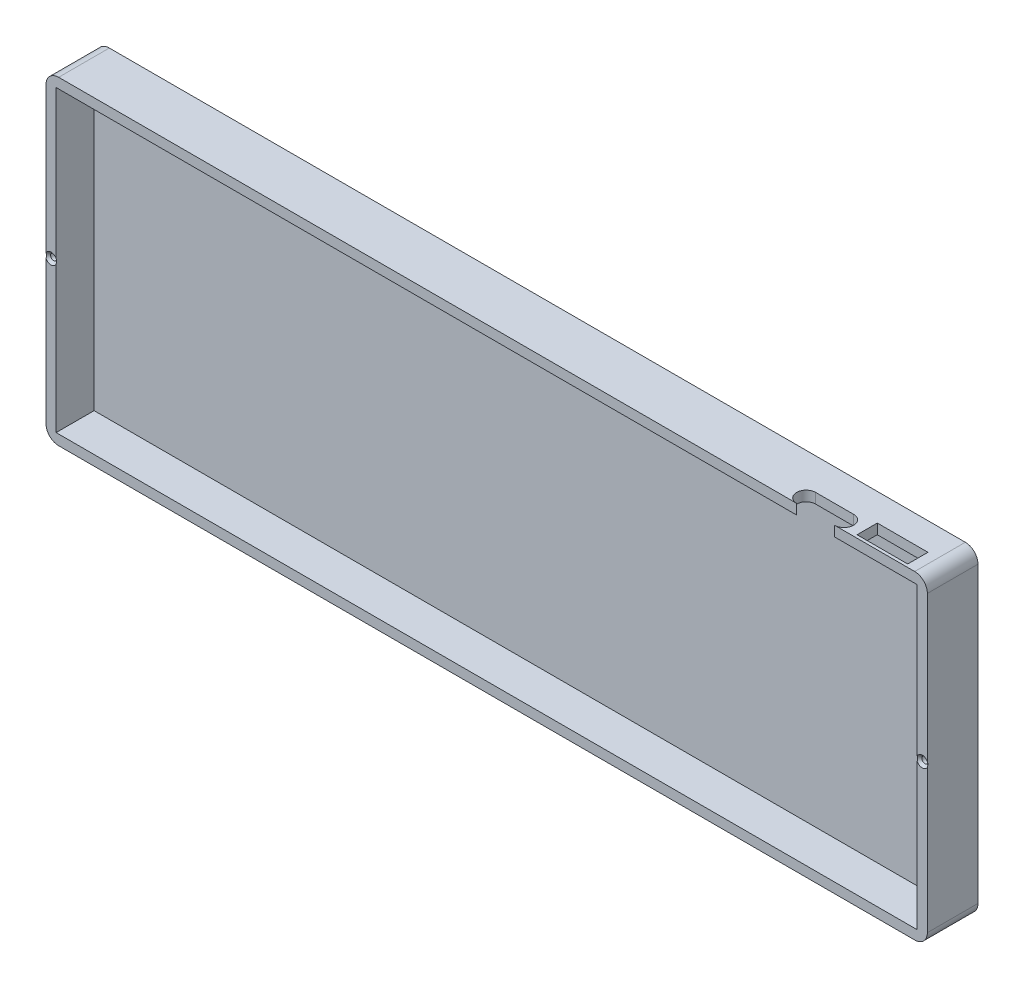
SolidWorks part; units mm, degrees
ref_plane "Front Plane" through (0, 0, 0) normal (0, 0, 1) x (1, 0, 0)
ref_plane "Top Plane" through (0, 0, 0) normal (0, 1, 0) x (1, 0, 0)
ref_plane "Right Plane" through (0, 0, 0) normal (1, 0, 0) x (0, 0, -1)
sketch "Sketch1" plane through (0, 0, 0) normal (0, 0, 1) x (1, 0, 0)
  line L1 (174, 63) -> (-174, 63)
  line L2 (174, 63) -> (174, -63)
  line L3 (174, -63) -> (-174, -63)
  line L4 (-174, 63) -> (-174, -63)
  line L5 (174, 63) -> (-174, -63) construction
  line L6 (174, -63) -> (-174, 63) construction
  point P0 (0, 0)
  dimension "D1" = 348
  dimension "D2" = 126
extrude "Boss-Extrude1" add sketch "Sketch1" along normal blind 20
sketch "Sketch2" plane through (0, 0, 20) normal (0, 0, 1) x (1, 0, 0)
  line L1 (170, 59) -> (-170, 59)
  line L2 (170, 59) -> (170, -59)
  line L3 (170, -59) -> (-170, -59)
  line L4 (-170, 59) -> (-170, -59)
  line L5 (170, 59) -> (-170, -59) construction
  line L6 (170, -59) -> (-170, 59) construction
  point P0 (0, 0)
  dimension "D1" = 340
  dimension "D2" = 118
extrude "Cut-Extrude1" cut sketch "Sketch2" against normal blind 15
sketch "Sketch4" plane through (0, 63, 0) normal (0, 1, 0) x (1, 0, 0)
  line L0 (122.39, -16.25) -> (137.39, -16.25) construction
  line L1 (122.39, -12.5) -> (137.39, -12.5)
  line L2 (122.39, -20) -> (137.39, -20)
  line L3 (174, -20) -> (174, 0) construction
  line L4 (174, -20) -> (-174, -20) construction
  arc A0 (122.39, -12.5) -> (122.39, -20) centre (122.39, -16.25) ccw
  arc A1 (137.39, -20) -> (137.39, -12.5) centre (137.39, -16.25) ccw
  point P2 (129.89, -16.25)
  dimension "D1" = 36.61
  dimension "D3" = 15
  dimension "D2" = 0
  dimension "D4" = 7.5
extrude "Cut-Extrude2" cut sketch "Sketch4" against normal up to next contours L2 A1 L1 A0
sketch "Sketch5" plane through (0, 63, 0) normal (0, 1, 0) x (1, 0, 0)
  line L0 (174, -20) -> (174, 0) construction
  line L1 (145.05, -10.81) -> (165.05, -10.81)
  line L2 (145.05, -10.81) -> (145.05, -18.81)
  line L3 (145.05, -18.81) -> (165.05, -18.81)
  line L4 (165.05, -10.81) -> (165.05, -18.81)
  line L6 (174, -20) -> (137.39, -20) construction
  dimension "D1" = 8.95
  dimension "D3" = 1.19
  dimension "D4" = 8
  dimension "D5" = 20
extrude "Cut-Extrude3" cut sketch "Sketch5" against normal up to next
fillet "Fillet1" radius 5 4 edges at (-174, 63, 10) (-174, -63, 10) (174, -63, 10) (174, 63, 10)
sketch "Sketch9" plane through (0, 0, 20) normal (0, 0, 1) x (1, 0, 0)
  line L0 (170, 59) -> (-170, 59) construction
  line L1 (-174, 58) -> (-174, -58) construction
  line L2 (170, 59) -> (137.39, 59) construction
  line L3 (170, -59) -> (170, 59) construction
  point P0 (-172, -0.475)
  point P5 (172, -0.475)
  point P10 (170.2158, -0.4599)
  dimension "D1" = 59.475
  dimension "D2" = 2
  dimension "D3" = 59.475
  dimension "D4" = 2
hole_wizard "CSK for M2 Flat Head Machine Screw2" positions "Sketch9" profile "Sketch10" countersink size "M2" standard "ANSI Metric"
sketch "Sketch10" plane through (-172, -0.475, 20) normal (1, 0, 0) x (0, -1, 0)
  line L0 (0, 0) -> (0, 18)
  line L1 (0, 18) -> (1.2, 17.279)
  line L2 (1.2, 17.279) -> (1.2, 1)
  line L3 (1.2, 1) -> (2.2, 0)
  line L5 (2.2, 0) -> (0, 0)
  line L6 (-1.2, 1) -> (-2.2, 0) construction
  line L10 (0, 18) -> (-1.2, 17.279) construction
  line L11 (0, -6.35) -> (0, 107.95) construction
  dimension "Hole Dia." = 2.4
  dimension "Hole Depth" = 18
  dimension "Near C'Sink Dia." = 4.4
  dimension "Near C'Sink Angle" = 90
  dimension "Drill Angle" = 118
